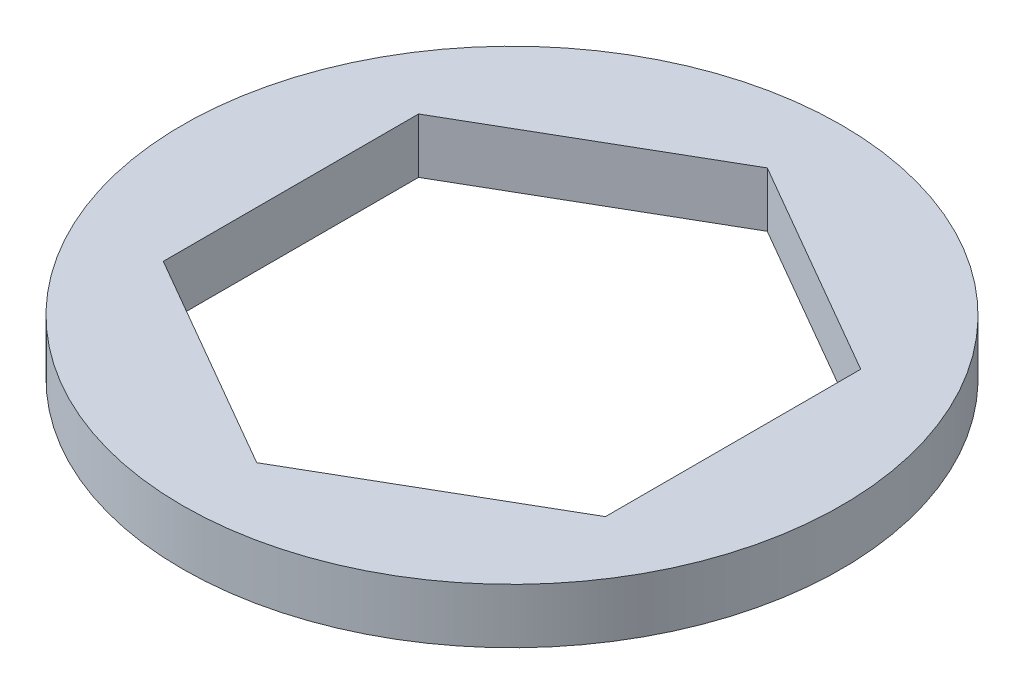
SolidWorks part; units mm, degrees
material "PET"
ref_plane "Front Plane" through (0, 0, 0) normal (0, 0, 1) x (1, 0, 0)
ref_plane "Top Plane" through (0, 0, 0) normal (0, 1, 0) x (1, 0, 0)
ref_plane "Right Plane" through (0, 0, 0) normal (1, 0, 0) x (0, 0, -1)
sketch "Sketch1" plane through (0, 0, 0) normal (0, 1, 0) x (1, 0, 0)
  line L1 (6.3897, 3.6891) -> (0, 7.3782)
  line L2 (0, 7.3782) -> (-6.3897, 3.6891)
  line L3 (-6.3897, 3.6891) -> (-6.3897, -3.6891)
  line L4 (-6.3897, -3.6891) -> (0, -7.3782)
  line L5 (0, -7.3782) -> (6.3897, -3.6891)
  line L6 (6.3897, -3.6891) -> (6.3897, 3.6891)
  circle A0 centre (0, 0) radius 9.525
  circle A2 centre (0, 0) radius 6.3897 construction
  dimension "D1" = 12.7794
  dimension "D2" = 19.05
extrude "Boss-Extrude1" add sketch "Sketch1" along normal blind 1.5875
